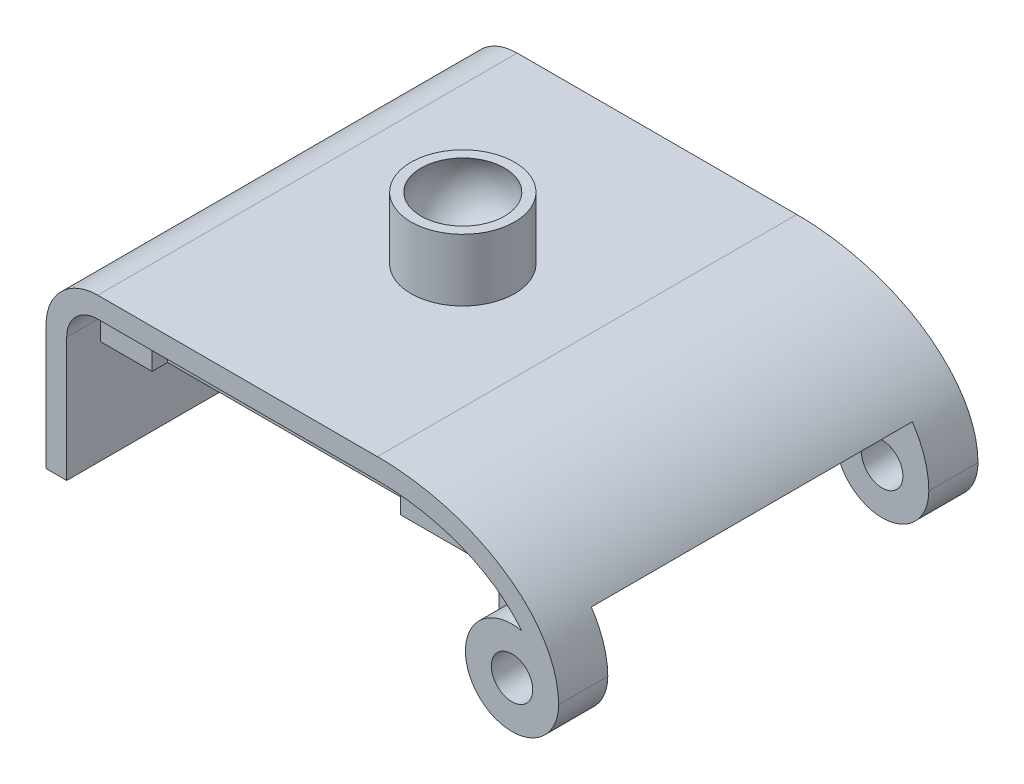
SolidWorks part; units mm, degrees
ref_plane "前视基准面" through (0, 0, 0) normal (0, 0, 1) x (1, 0, 0)
ref_plane "上视基准面" through (0, 0, 0) normal (0, 1, 0) x (1, 0, 0)
ref_plane "右视基准面" through (0, 0, 0) normal (1, 0, 0) x (0, 0, -1)
sketch "草图1" plane through (0, 0, 0) normal (0, 0, 1) x (1, 0, 0)
  line L0 (0, 0) -> (0, 12)
  line L1 (5, 17) -> (32, 17)
  line L2 (0, 0) -> (2, 0)
  line L3 (2, 0) -> (2, 12)
  line L4 (5, 15) -> (32, 15)
  arc A0 (0, 12) -> (5, 17) centre (5, 12) cw
  arc A2 (2, 12) -> (5, 15) centre (5, 12) cw
  arc A6 (45.9143, 9.4061) -> (49.5, 5) centre (45, 5) ccw
  ellipse E0 centre (32, 5) end of major axis (49.5, 5) minor radius 12 (32, 17) -> (49.5, 5) cw
  ellipse E2 centre (32, 5) end of major axis (47.5, 5) minor radius 10 (32, 15) -> (45.9143, 9.4061) cw
  dimension "D2" = 5
  dimension "D4" = 27
  dimension "D9" = 3
  dimension "D1" = 12
  dimension "D3" = 27
  dimension "D8" = 2
extrude "凸台-拉伸1" add sketch "草图1" along normal blind 37.25 and the other way blind 3.25
ref_plane "基准面1" through (0, 0, 17) normal (0, 0, 1) x (1, 0, 0)
sketch "草图3" plane through (0, 0, 0) normal (0, 0, 1) x (1, 0, 0)
  line L1 (2, 0) -> (2, 12) construction
  line L2 (2, 10) -> (2, 12)
  line L3 (5, 15) -> (34, 15)
  line L8 (34, 15) -> (39.1049, 15.7038)
  line L9 (39.1049, 15.7038) -> (46.1146, 11.473)
  line L10 (46.1146, 11.473) -> (46.1146, 10)
  line L11 (40.5, 9) -> (40.5, 5)
  line L12 (40.5, 5) -> (46.1146, 5)
  line L13 (46.1146, 5) -> (46.1146, 10)
  line L14 (0, 0) -> (2, 0) construction
  line L15 (39.5, 10) -> (2, 10)
  line L16 (39.5, 10) -> (40.5, 10)
  line L17 (40.5, 10) -> (40.5, 9)
  arc A0 (2, 12) -> (5, 15) centre (5, 12) cw
  arc A1 (5, 15) -> (2, 12) centre (5, 12) ccw construction
  point P20 (1, 0)
  dimension "D1" = 5
extrude "凸台-拉伸2" add sketch "草图3" along normal blind 34
sketch "草图4" plane through (0, 0, 0) normal (0, 0, 1) x (1, 0, 0)
  line L1 (7, 10) -> (31, 10)
  line L2 (7, 10) -> (7, 13)
  line L3 (7, 13) -> (31, 13)
  line L4 (31, 10) -> (31, 13)
  line L5 (2, 0) -> (2, 12) construction
  dimension "D1" = 3
  dimension "D2" = 24
  dimension "D3" = 5
extrude "切除-拉伸2" cut sketch "草图4" along normal blind 1.5
sketch "草图5" plane through (0, 0, 34) normal (0, 0, 1) x (1, 0, 0)
  line L1 (7, 10) -> (31, 10)
  line L2 (7, 10) -> (7, 13)
  line L3 (7, 13) -> (31, 13)
  line L4 (31, 10) -> (31, 13)
  line L5 (2, 0) -> (2, 12) construction
  dimension "D1" = 3
  dimension "D2" = 24
  dimension "D3" = 5
extrude "切除-拉伸3" cut sketch "草图5" against normal blind 1.5
sketch "草图6" plane through (0, 0, 0) normal (-1, 0, 0) x (0, 0, 1)
  text T0 "小R科技"
extrude "切除-拉伸4" cut sketch "草图6" against normal blind 1
sketch "草图8" plane through (0, 17, 0) normal (0, 1, 0) x (1, 0, 0)
  line L0 (5, 3.25) -> (5, -37.25) construction
  line L1 (32, 3.25) -> (5, 3.25) construction
  circle A0 centre (20, -17) radius 5
  point P4 (5, -17)
  dimension "D1" = 10
  dimension "D2" = 15
  dimension "D3" = 20.25
extrude "凸台-拉伸3" add sketch "草图8" along normal blind 6 contours A0
ref_axis "基准轴1" through (20, 23, 17) along (0, -1, 0)
sketch "草图9" plane through (0, 0, 17) normal (0, 0, 1) x (1, 0, 0)
  line L1 (20, 25.5) -> (20, 16.5)
  line L2 (25, 17) -> (15, 17) construction
  arc A1 (20, 25.5) -> (20, 16.5) centre (20, 21) ccw
  dimension "D1" = 4.5
  dimension "D2" = 4
revolve "切除-旋转5" cut sketch "草图9" angle 360 about L1
sketch "草图10" plane through (0, 0, 17) normal (0, 0, 1) x (1, 0, 0)
  line L8 (40.5, 5) -> (40.5, 10)
  line L10 (49.5, 10) -> (49.5, 5)
  line L11 (40.5, 10) -> (49.5, 10)
  arc A3 (40.5, 5) -> (49.5, 5) centre (45, 5) ccw
  arc A4 (45.9143, 9.4061) -> (49.5, 5) centre (45, 5) ccw construction
  ellipse E0 centre (32, 5) end of major axis (49.5, 5) minor radius 12 (49.5, 5) -> (32, 17) ccw construction
  dimension "D2" = 9
  dimension "D3" = 5
extrude "切除-拉伸5" cut sketch "草图10" along normal up to surface and the other way up to surface up to face at (19, 11.5, 32.5) other way up to face at (19, 11.5, 1.5)
sketch "草图11" plane through (0, 0, -3.25) normal (0, 0, -1) x (-1, 0, 0)
  circle A0 centre (-45, 5) radius 2
  dimension "D1" = 4
extrude "切除-拉伸6" cut sketch "草图11" against normal up to surface (40.5 mm away) up to face at (17.0425, 10.2789, 37.25)
fillet "圆角1" radius 1 2 edges at (40.5, 10, 0.75) (40.5, 10, 33.25)
